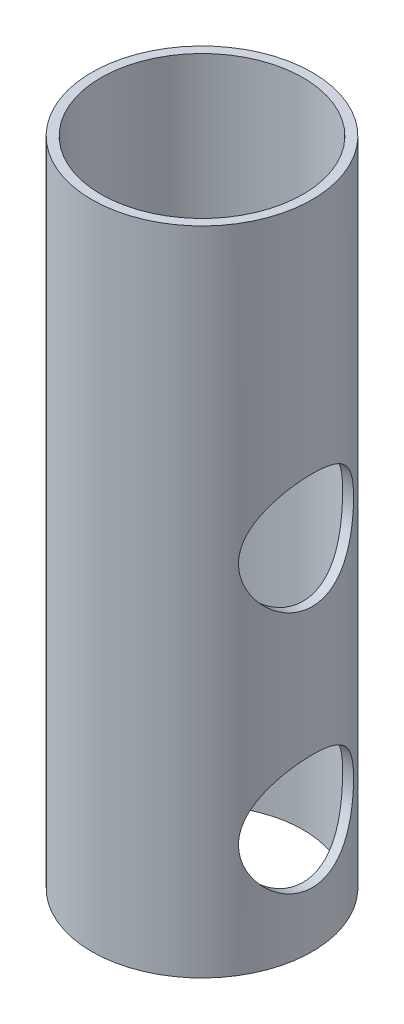
SolidWorks part; units mm, degrees
material "PTFE (general)"
ref_plane "Front Plane" through (0, 0, 0) normal (0, 0, 1) x (1, 0, 0)
ref_plane "Top Plane" through (0, 0, 0) normal (0, 1, 0) x (1, 0, 0)
ref_plane "Right Plane" through (0, 0, 0) normal (1, 0, 0) x (0, 0, -1)
sketch "Sketch1" plane through (0, 0, 0) normal (0, 1, 0) x (1, 0, 0)
  circle A0 centre (0, 0) radius 24
  circle A1 centre (0, 0) radius 22
  dimension "D1" = 2
  dimension "D2" = 44
extrude "Boss-Extrude1" add sketch "Sketch1" along normal blind 141.8
sketch "Sketch2" plane through (0, 0, 0) normal (1, 0, 0) x (0, 0, -1)
  line L1 (24, 141.8) -> (-24, 141.8) construction
  circle A0 centre (0, 24.6) radius 12.53
  circle A1 centre (0, 77.6) radius 12.53
  dimension "D2" = 25.06
  dimension "D3" = 25.06
  dimension "D1" = 64.2
  dimension "D5" = 53
extrude "Cut-Extrude1" cut sketch "Sketch2" along normal through all
